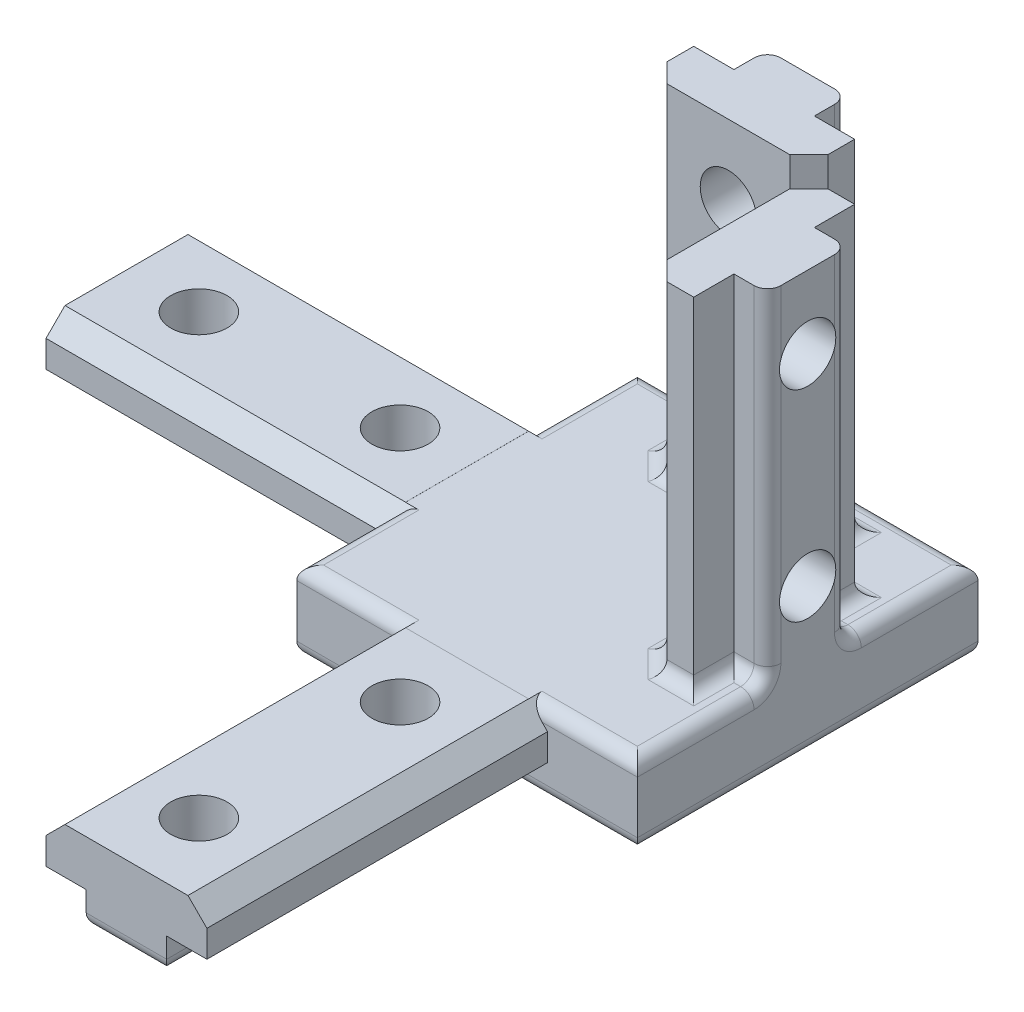
SolidWorks part; units mm, degrees
ref_plane "Front Plane" through (0, 0, 0) normal (0, 0, 1) x (1, 0, 0)
ref_plane "Top Plane" through (0, 0, 0) normal (0, 1, 0) x (1, 0, 0)
ref_plane "Right Plane" through (0, 0, 0) normal (1, 0, 0) x (0, 0, -1)
sketch "Sketch1" plane through (0, 0, 0) normal (0, 1, 0) x (1, 0, 0)
  line L1 (-12.7, 12.7) -> (12.7, 12.7)
  line L2 (-12.7, 12.7) -> (-12.7, -12.7)
  line L3 (-12.7, -12.7) -> (12.7, -12.7)
  line L4 (12.7, 12.7) -> (12.7, -12.7)
  line L5 (-12.7, 12.7) -> (12.7, -12.7) construction
  line L6 (-12.7, -12.7) -> (12.7, 12.7) construction
  point P0 (0, 0)
  dimension "D1" = 25.4
extrude "Boss-Extrude1" add sketch "Sketch1" along normal blind 5.91
sketch "Sketch2" plane through (0, 0, 12.7) normal (0, 0, 1) x (1, 0, 0)
  line L0 (-3, 0) -> (3, 0)
  line L1 (-12.7, 0) -> (12.7, 0) construction
  line L2 (3, 0) -> (3, 2.5)
  line L3 (3, 2.5) -> (6, 2.5)
  line L4 (6, 2.5) -> (6, 4.5)
  line L5 (6, 4.5) -> (4.5858, 5.9142)
  line L6 (4.5858, 5.9142) -> (-4.5858, 5.9142)
  line L7 (0, 0) -> (0, 6.6193) construction
  line L8 (-6, 4.5) -> (-4.5858, 5.9142)
  line L9 (-6, 2.5) -> (-6, 4.5)
  line L10 (-3, 2.5) -> (-6, 2.5)
  line L11 (-3, 0) -> (-3, 2.5)
  point P14 (0, 5.9142)
  point P18 (0, 0)
  dimension "D1" = 6
  dimension "D2" = 12
  dimension "D3" = 135
  dimension "D4" = 2.5
  dimension "D5" = 2
extrude "Boss-Extrude2" add sketch "Sketch2" along normal blind 25.4
sketch "Sketch3" plane through (-12.7, 0, 0) normal (-1, 0, 0) x (0, 0, 1)
  line L0 (-3, 0) -> (3, 0)
  line L1 (3, 0) -> (3, 2.5)
  line L2 (3, 2.5) -> (6, 2.5)
  line L3 (6, 2.5) -> (6, 4.5)
  line L4 (6, 4.5) -> (4.5858, 5.9142)
  line L5 (4.5858, 5.9142) -> (-4.5858, 5.9142)
  line L6 (0, 0) -> (0, 6.6193) construction
  line L7 (-6, 4.5) -> (-4.5858, 5.9142)
  line L8 (-6, 2.5) -> (-6, 4.5)
  line L9 (-3, 2.5) -> (-6, 2.5)
  line L10 (-3, 0) -> (-3, 2.5)
  point P9 (0, 5.9142)
  point P13 (0, 0)
  dimension "D1" = 6
  dimension "D2" = 12
  dimension "D3" = 2.5
  dimension "D4" = 2
  dimension "D5" = 135
extrude "Boss-Extrude3" add sketch "Sketch3" along normal blind 25.4
sketch "Sketch5" plane through (0, 5.91, 0) normal (0, 1, 0) x (1, 0, 0)
  line L0 (3, 12.7) -> (-3, 12.7)
  line L1 (-3, 12.7) -> (-3, 10.2)
  line L2 (-3, 10.2) -> (-6, 10.2)
  line L3 (-6, 10.2) -> (-6, 8.2)
  line L4 (-6, 8.2) -> (-4.5858, 6.7858)
  line L5 (-4.5858, 6.7858) -> (4.5858, 6.7858)
  line L6 (0, 3.4686) -> (0, -3.1261) construction
  line L7 (6, 8.2) -> (4.5858, 6.7858)
  line L8 (6, 10.2) -> (6, 8.2)
  line L9 (3, 10.2) -> (6, 10.2)
  line L10 (3, 12.7) -> (3, 10.2)
  line L11 (12.7, 12.7) -> (-12.7, 12.7) construction
  line L12 (12.7, -3) -> (12.7, 3)
  line L13 (12.7, 3) -> (10.2, 3)
  line L14 (10.2, 3) -> (10.2, 6)
  line L15 (10.2, 6) -> (8.2, 6)
  line L16 (8.2, 6) -> (6.7858, 4.5858)
  line L17 (6.7858, 4.5858) -> (6.7858, -4.5858)
  line L18 (6.7858, 0) -> (12.7, 0) construction
  line L19 (8.2, -6) -> (6.7858, -4.5858)
  line L20 (10.2, -6) -> (8.2, -6)
  line L21 (10.2, -3) -> (10.2, -6)
  line L22 (12.7, -3) -> (10.2, -3)
  line L23 (12.7, -12.7) -> (12.7, 12.7) construction
  point P9 (0, 6.7858)
  point P13 (0, 12.7)
  point P27 (6.7858, 0)
  point P31 (12.7, 0)
  dimension "D1" = 6
  dimension "D2" = 12
  dimension "D3" = 2.5
  dimension "D4" = 2
  dimension "D5" = 135
  dimension "D6" = 2.5
  dimension "D7" = 6
  dimension "D8" = 12
  dimension "D9" = 2
  dimension "D10" = 135
  dimension "D11" = 135
extrude "Boss-Extrude4" add sketch "Sketch5" along normal blind 25.4
fillet "Fillet2" radius 1 42 edges at (3, 18.61, -12.7) (12.7, 18.61, -3) (12.7, 18.61, 3) (-3, 18.61, -12.7) (-6, 5.91, -9.2) (-5.2929, 5.91, -7.4929) (0, 5.91, -6.7858) (5.2929, 5.91, -7.4929) (6, 5.91, -9.2) (4.5, 5.91, -10.2) (3, 5.91, -11.45) (7.85, 5.91, -12.7) (12.7, 5.91, -7.85) (11.45, 5.91, -3) (10.2, 5.91, -4.5) (9.2, 5.91, -6) (7.4929, 5.91, -5.2929) (6.7858, 5.91, 0) (7.4929, 5.91, 5.2929) (9.2, 5.91, 6) (10.2, 5.91, 4.5) (11.45, 5.91, 3) (12.7, 5.91, 7.85) (8.645, 5.91, 12.7) (-8.645, 5.91, 12.7) (-12.7, 5.91, 8.645) (-12.7, 5.91, -8.645) (-7.85, 5.91, -12.7) (-3, 5.91, -11.45) (-4.5, 5.91, -10.2) (0, 0, -12.7) (-12.7, 0, -7.85) (-25.4, 0, -3) (-38.1, 0, 0) (-25.4, 0, 3) (-12.7, 0, 7.85) (-7.85, 0, 12.7) (-3, 0, 25.4) (0, 0, 38.1) (3, 0, 25.4) (7.85, 0, 12.7) (12.7, 0, 0)
hole_wizard "M5x0.8 Tapped Hole2" positions "Sketch8" profile "Sketch9" tap size "M5x0.8" standard "ANSI Metric" end condition through all
sketch "Sketch8" plane through (0, 0, 0) normal (0, -1, 0) x (-1, 0, 0)
  line L0 (12.7, 6) -> (12.7, 3) construction
  line L1 (6, -12.7) -> (3, -12.7) construction
  point P0 (0, -17.7)
  point P2 (0, -32.7)
  point P4 (17.7, 0)
  point P6 (32.7, 0)
  point P17 (-10.3114, -30.8057)
  point P20 (0, 0)
  point P22 (0, 0)
  dimension "D1" = 5
  dimension "D2" = 15
  dimension "D3" = 5
  dimension "D4" = 15
sketch "Sketch9" plane through (0, 0, 17.7) normal (1, 0, 0) x (0, 0, -1)
  line L0 (0, 0) -> (0, 31.31)
  line L1 (0, 31.31) -> (2.1, 31.31)
  line L2 (2.1, 31.31) -> (2.1, 0)
  line L5 (2.1, 0) -> (0, 0)
  line L11 (0, -6.35) -> (0, 107.95) construction
  dimension "Thru Tap Drill Dia." = 4.2
  dimension "Thru Tap Drill Depth" = 31.31
cosmetic thread "Hole Thread3" parameters "D2"=5
cosmetic thread "Hole Thread4" parameters "D2"=5
cosmetic thread "Hole Thread5" parameters "D2"=5
cosmetic thread "Hole Thread6" parameters "D2"=5
hole_wizard "M5x0.8 Tapped Hole3" positions "Sketch10" profile "Sketch11" tap size "M5x0.8" standard "ANSI Metric" end condition through all
sketch "Sketch10" plane through (12.7, 0, 0) normal (1, 0, 0) x (0, 0, -1)
  line L0 (-4, 5.91) -> (-7, 5.91) construction
  point P0 (0, 10.91)
  point P2 (0, 25.91)
  point P7 (0, 0)
  dimension "D1" = 5
  dimension "D2" = 15
sketch "Sketch11" plane through (12.7, 10.91, 0) normal (0, 1, 0) x (0, 0, -1)
  line L0 (0, 0) -> (0, 50.8)
  line L1 (0, 50.8) -> (2.1, 50.8)
  line L2 (2.1, 50.8) -> (2.1, 0)
  line L5 (2.1, 0) -> (0, 0)
  line L11 (0, -6.35) -> (0, 107.95) construction
  dimension "Thru Tap Drill Dia." = 4.2
  dimension "Thru Tap Drill Depth" = 50.8
cosmetic thread "Hole Thread7" parameters "D2"=5
cosmetic thread "Hole Thread8" parameters "D2"=5
hole_wizard "M5x0.8 Tapped Hole4" positions "Sketch12" profile "Sketch13" tap size "M5x0.8" standard "ANSI Metric" end condition through all
sketch "Sketch12" plane through (0, 0, -12.7) normal (0, 0, -1) x (-1, 0, 0)
  line L0 (-4, 5.91) -> (-7, 5.91) construction
  point P0 (0, 25.91)
  point P2 (0, 10.91)
  point P7 (0, 0)
  dimension "D1" = 5
  dimension "D2" = 15
sketch "Sketch13" plane through (0, 25.91, -12.7) normal (1, 0, 0) x (0, 1, 0)
  line L0 (0, 0) -> (0, 50.8)
  line L1 (0, 50.8) -> (2.1, 50.8)
  line L2 (2.1, 50.8) -> (2.1, 0)
  line L5 (2.1, 0) -> (0, 0)
  line L11 (0, -6.35) -> (0, 107.95) construction
  dimension "Thru Tap Drill Dia." = 4.2
  dimension "Thru Tap Drill Depth" = 50.8
cosmetic thread "Hole Thread9" parameters "D2"=5
cosmetic thread "Hole Thread10" parameters "D2"=5
equation "\"Insert Lengths\"= 1in"
equation "\"D1@Boss-Extrude2\"=\"Insert Lengths\""
equation "\"D1@Boss-Extrude4\"=\"Insert Lengths\""
